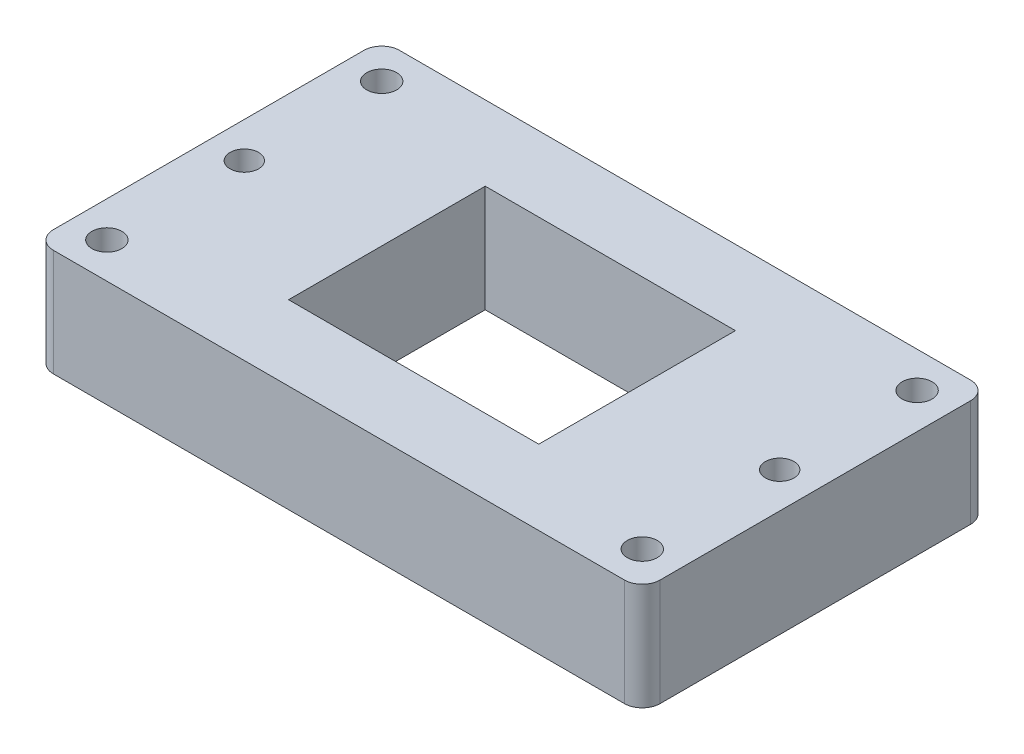
SolidWorks part; units mm, degrees
material "Plain Carbon Steel"
ref_plane "Front Plane" through (0, 0, 0) normal (0, 0, 1) x (1, 0, 0)
ref_plane "Top Plane" through (0, 0, 0) normal (0, 1, 0) x (1, 0, 0)
ref_plane "Right Plane" through (0, 0, 0) normal (1, 0, 0) x (0, 0, -1)
sketch "Sketch1" plane through (0, 0, 0) normal (0, 1, 0) x (1, 0, 0)
  line L1 (-85, -48.5) -> (85, -48.5)
  line L2 (-85, -48.5) -> (-85, 48.5)
  line L3 (-85, 48.5) -> (85, 48.5)
  line L4 (85, -48.5) -> (85, 48.5)
  line L5 (-85, -48.5) -> (85, 48.5) construction
  line L6 (-85, 48.5) -> (85, -48.5) construction
  point P0 (0, 0)
  dimension "D1" = 170
  dimension "D2" = 97
extrude "Boss-Extrude1" add sketch "Sketch1" against normal blind 30
fillet "Fillet1" radius 5 4 edges at (-85, -15, -48.5) (-85, -15, 48.5) (85, -15, -48.5) (85, -15, 48.5)
sketch "Sketch2" plane through (0, -30, 0) normal (0, 1, 0) x (1, 0, 0)
  line L8 (35.05, 27.55) -> (-35.05, 27.55)
  line L9 (-35.05, 27.55) -> (-35.05, -27.55)
  line L10 (-35.05, -27.55) -> (35.05, -27.55)
  line L11 (35.05, -27.55) -> (35.05, 27.55)
  point P2 (-35.05, 0)
  point P4 (0, -27.55)
  dimension "D1" = 70.1
  dimension "D2" = 55.1
extrude "Cut-Extrude3" cut sketch "Sketch2" along normal through all
hole_wizard "Ø8.0mm Dowel Hole1" positions "Sketch5" profile "Sketch4" hole size "Ø8.0" standard "ISO" end condition through all
sketch "Sketch5" plane through (0, 0, 0) normal (0, 1, 0) x (1, 0, 0)
  point P0 (-75, 0)
  point P3 (75, 0)
sketch "Sketch4" plane through (-75, 0, 0) normal (1, 0, 0) x (0, 0, 1)
  line L0 (0, 0) -> (0, 30)
  line L1 (0, 30) -> (4, 30)
  line L2 (4, 30) -> (4, 0)
  line L5 (4, 0) -> (0, 0)
  line L11 (0, -6.35) -> (0, 107.95) construction
  dimension "Thru Hole Dia." = 8
  dimension "Thru Hole Depth" = 30
hole_wizard "M8 Clearance Hole1" positions "Sketch8" profile "Sketch7" hole size "M8" standard "ISO" end condition through all
sketch "Sketch8" plane through (0, 0, 0) normal (0, 1, 0) x (1, 0, 0)
  point P0 (-75, 38.5)
  point P3 (-75, -38.5)
  point P6 (75, -38.5)
  point P9 (75, 38.5)
sketch "Sketch7" plane through (-75, 0, -38.5) normal (1, 0, 0) x (0, 0, 1)
  line L0 (0, 0) -> (0, 30)
  line L1 (0, 30) -> (4.2, 30)
  line L2 (4.2, 30) -> (4.2, 0)
  line L5 (4.2, 0) -> (0, 0)
  line L11 (0, -6.35) -> (0, 107.95) construction
  dimension "Thru Hole Dia." = 8.4
  dimension "Thru Hole Depth" = 30
